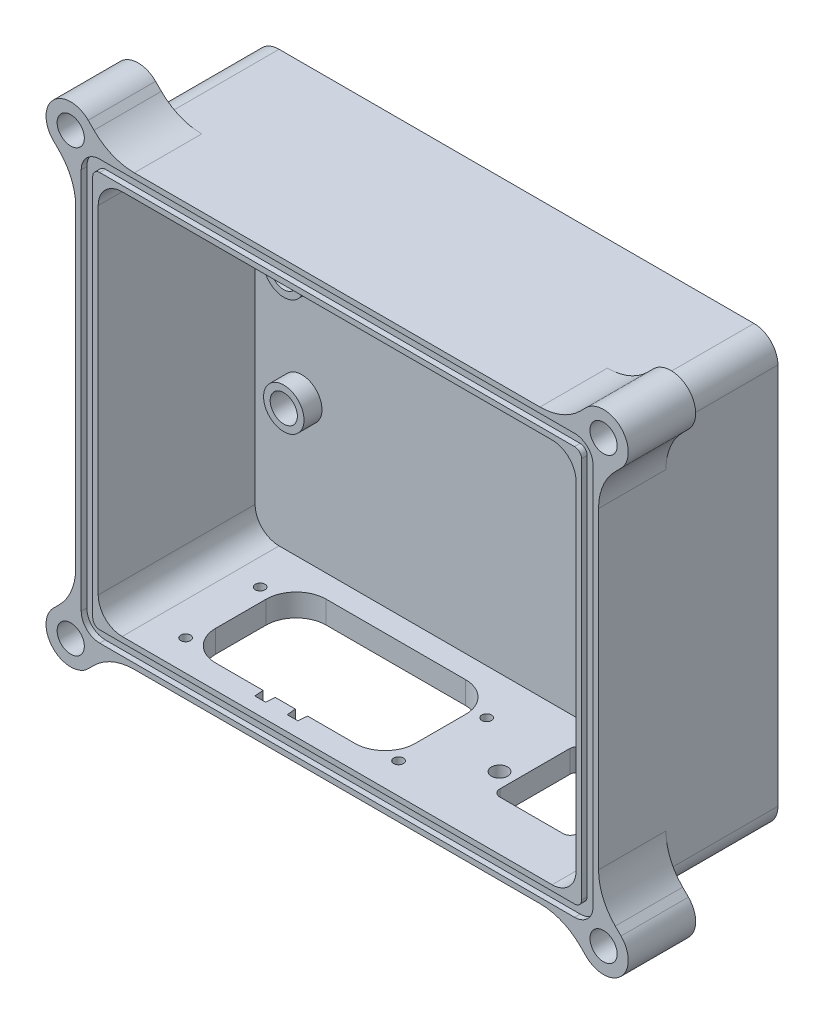
SolidWorks part; units mm, degrees
material "ABS"
ref_plane "X-Y Datum" through (0, 0, 0) normal (0, 0, 1) x (1, 0, 0)
ref_plane "X-Z Datum" through (0, 0, 0) normal (0, 1, 0) x (1, 0, 0)
ref_plane "Y-Z Datum" through (0, 0, 0) normal (1, 0, 0) x (0, 0, -1)
sketch "Sketch1" plane through (0, 0, 0) normal (0, 0, 1) x (1, 0, 0)
  line L1 (-53.1813, 42.8625) -> (53.1812, 42.8625)
  line L2 (-53.1813, 42.8625) -> (-53.1812, -42.8625)
  line L3 (-53.1812, -42.8625) -> (53.1813, -42.8625)
  line L4 (53.1812, 42.8625) -> (53.1813, -42.8625)
  line L5 (-53.1813, 42.8625) -> (53.1813, -42.8625) construction
  line L6 (-53.1812, -42.8625) -> (53.1812, 42.8625) construction
  point P0 (0, 0)
  dimension "D1" = 106.3625
  dimension "D2" = 85.725
extrude "Boss-Extrude1" add sketch "Sketch1" along normal blind 34.925
shell "Shell1" thickness 5 removed face at (0, 0, 34.925) outward yes
fillet "Fillet1" radius 5.334 8 edges at (-58.1812, -47.8625, 14.9625) (58.1813, -47.8625, 14.9625) (53.1812, 42.8625, 17.4625) (58.1812, 47.8625, 14.9625) (-58.1813, 47.8625, 14.9625) (-53.1813, 42.8625, 17.4625) (53.1813, -42.8625, 17.4625) (-53.1812, -42.8625, 17.4625)
sketch "Sketch2" plane through (0, 0, 34.925) normal (0, 0, 1) x (1, 0, 0)
  line L20 (-52.8472, -46.6452) -> (52.8472, -46.6452)
  line L21 (56.9639, -42.5285) -> (56.9639, 42.5285)
  line L22 (52.8472, 46.6452) -> (-52.8473, 46.6452)
  line L23 (-56.9639, 42.5285) -> (-56.9639, -42.5285)
  line L24 (-52.8472, -45.3625) -> (52.8473, -45.3625)
  line L25 (55.6812, -42.5285) -> (55.6812, 42.5285)
  line L26 (52.8472, 45.3625) -> (-52.8473, 45.3625)
  line L27 (-55.6812, 42.5285) -> (-55.6812, -42.5285)
  line L28 (-52.8472, -45.3625) -> (52.8473, -45.3625) construction
  line L29 (55.6812, -42.5285) -> (55.6812, 42.5285) construction
  line L30 (52.8472, 45.3625) -> (-52.8473, 45.3625) construction
  line L31 (-55.6812, 42.5285) -> (-55.6812, -42.5285) construction
  line L32 (-54.3986, 42.5285) -> (-54.3986, -42.5285)
  line L33 (-52.8472, -44.0798) -> (52.8472, -44.0798)
  line L34 (54.3986, -42.5285) -> (54.3986, 42.5285)
  line L35 (52.8472, 44.0798) -> (-52.8473, 44.0798)
  arc A16 (52.8472, -46.6452) -> (56.9639, -42.5285) centre (52.8473, -42.5285) ccw
  arc A17 (56.9639, 42.5285) -> (52.8472, 46.6452) centre (52.8472, 42.5285) ccw
  arc A18 (-52.8473, 46.6452) -> (-56.9639, 42.5285) centre (-52.8473, 42.5285) ccw
  arc A19 (-56.9639, -42.5285) -> (-52.8472, -46.6452) centre (-52.8472, -42.5285) ccw
  arc A20 (-55.6812, -42.5285) -> (-52.8472, -45.3625) centre (-52.8472, -42.5285) ccw
  arc A21 (52.8473, -45.3625) -> (55.6812, -42.5285) centre (52.8473, -42.5285) ccw
  arc A22 (55.6812, 42.5285) -> (52.8472, 45.3625) centre (52.8472, 42.5285) ccw
  arc A23 (-52.8473, 45.3625) -> (-55.6812, 42.5285) centre (-52.8473, 42.5285) ccw
  arc A24 (-55.6812, -42.5285) -> (-52.8472, -45.3625) centre (-52.8472, -42.5285) ccw construction
  arc A25 (52.8473, -45.3625) -> (55.6812, -42.5285) centre (52.8473, -42.5285) ccw construction
  arc A26 (55.6812, 42.5285) -> (52.8472, 45.3625) centre (52.8472, 42.5285) ccw construction
  arc A27 (-52.8473, 45.3625) -> (-55.6812, 42.5285) centre (-52.8473, 42.5285) ccw construction
  arc A28 (-52.8473, 44.0798) -> (-54.3986, 42.5285) centre (-52.8473, 42.5285) ccw
  arc A29 (-54.3986, -42.5285) -> (-52.8472, -44.0798) centre (-52.8472, -42.5285) ccw
  arc A30 (52.8472, -44.0798) -> (54.3986, -42.5285) centre (52.8473, -42.5285) ccw
  arc A31 (54.3986, 42.5285) -> (52.8472, 44.0798) centre (52.8472, 42.5285) ccw
  dimension "D4" = 2.5654
  dimension "D1" = 2.5
  dimension "D2" = 1.2827
  dimension "D3" = 1.2827
extrude "Cut-Extrude1" cut sketch "Sketch2" against normal blind 1.2446
sketch "Sketch4" plane through (0, 0, 34.925) normal (0, 0, 1) x (1, 0, 0)
  line L4 (58.1813, -42.5285) -> (58.1812, 42.5285) construction
  line L6 (47.8473, -37.5285) -> (59.2937, -48.975)
  line L7 (55.4046, -52.8641) -> (50.4031, -47.8625)
  line L8 (-52.8472, -47.8625) -> (52.8473, -47.8625) construction
  line L9 (63.1828, -45.0859) -> (58.1813, -40.0843)
  line L10 (-52.8472, -47.8625) -> (52.8473, -47.8625)
  line L11 (58.1813, -42.5285) -> (58.1812, 42.5285)
  arc A2 (47.8473, -42.8625) -> (53.1813, -37.5285) centre (47.8473, -37.5285) ccw construction
  circle A3 centre (59.2937, -48.975) radius 3.025
  circle A4 centre (59.2937, -48.975) radius 5.5
  arc A5 (52.8472, -46.6452) -> (56.9639, -42.5285) centre (52.8473, -42.5285) ccw construction
  arc A6 (52.8473, -47.8625) -> (58.1813, -42.5285) centre (52.8473, -42.5285) ccw construction
  arc A7 (58.1812, 42.5285) -> (52.8472, 47.8625) centre (52.8472, 42.5285) ccw construction
  arc A8 (52.8473, -47.8625) -> (58.1813, -42.5285) centre (52.8473, -42.5285) ccw
  arc A9 (58.1812, 42.5285) -> (52.8472, 47.8625) centre (52.8472, 42.5285) ccw
  point P14 (51.619, -41.3002)
  point P23 (55.7582, -45.4394)
  dimension "D1" = 11
  dimension "D2" = 6.05
  dimension "D4" = 5
extrude "Boss-Extrude2" add sketch "Sketch4" against normal blind 15 separate body contours A9 L11 | A9 | A8 A4 L9 L11 | A8 L10 L7 A4 | A8 A4 A3 | A3 | L11 region at (60.4186, -46.2593, 34.925) region at (57.6777, -45.1365, 34.925) region at (59.5123, -42.505, 34.925) region at (52.8237, -49.1935, 34.925)
sketch "Sketch5" plane through (0, 0, 34.925) normal (0, 0, 1) x (1, 0, 0)
  line L3 (-52.8472, -47.8625) -> (52.8473, -47.8625) construction
  line L4 (63.1828, -45.0859) -> (58.1813, -40.0843) construction
  line L5 (55.4046, -52.8641) -> (50.4031, -47.8625) construction
  line L6 (47.8473, -37.5285) -> (59.2937, -48.975) construction
  line L10 (-52.8472, -47.8625) -> (52.8473, -47.8625)
  line L11 (63.1828, -45.0859) -> (58.1813, -40.0843)
  line L12 (55.4046, -52.8641) -> (50.4031, -47.8625)
  line L13 (47.8473, -37.5285) -> (59.2937, -48.975)
  circle A1 centre (59.2937, -48.975) radius 3.025
  circle A2 centre (59.2937, -48.975) radius 3.025
  circle A7 centre (59.2937, -48.975) radius 5.5
  circle A8 centre (59.2937, -48.975) radius 5.5
  arc A9 (52.8473, -47.8625) -> (58.1813, -42.5285) centre (52.8473, -42.5285) ccw construction
  arc A11 (52.8473, -47.8625) -> (58.1813, -42.5285) centre (52.8473, -42.5285) ccw
  dimension "D1" = 0
  dimension "D4" = 0
extrude "Cut-Extrude4" cut sketch "Sketch5" against normal blind 8 contours A2 region at (60.4186, -46.2593, 34.925)
mirror "Mirror3" about plane through (0, 0, 0) normal (1, 0, 0) of bodies 107 106
mirror "Mirror7" about plane through (0, 0, 0) normal (0, 1, 0) of bodies 107 109
combine bodies "Combine3" operation type add bodies to combine 102 107 109 121 122
fillet "Fillet2" radius 12.7 8 edges at (-50.4031, -47.8625, 27.425) (-58.1813, -40.0843, 27.425) (50.4031, -47.8625, 27.425) (58.1813, -40.0843, 27.425) (-58.1813, 40.0843, 27.425) (-50.4031, 47.8625, 27.425) (50.4031, 47.8625, 27.425) (58.1813, 40.0843, 27.425)
sketch "Sketch13" plane through (0, -47.8625, 0) normal (0, -1, 0) x (1, 0, 0)
  line L0 (-12.3227, 29.1278) -> (-12.4976, 31.1278) construction
  line L1 (-12.4976, 31.1278) -> (-13.9477, 31.1278) construction
  line L2 (-13.9477, 31.1278) -> (-14.1227, 29.1278) construction
  line L3 (-19.6976, 31.1278) -> (-21.1477, 31.1278) construction
  line L4 (-21.1477, 31.1278) -> (-21.3227, 29.1278) construction
  line L5 (-19.5227, 29.1278) -> (-19.6976, 31.1278) construction
  line L6 (-21.3227, 29.1278) -> (-32.3227, 29.1278) construction
  line L7 (-38.5227, 22.9278) -> (-38.5227, 11.7278) construction
  line L8 (-32.3227, 5.5278) -> (-1.3227, 5.5278) construction
  line L9 (4.8773, 11.7278) -> (4.8773, 22.9278) construction
  line L10 (-1.3227, 29.1278) -> (-12.3227, 29.1278) construction
  line L11 (-14.1227, 29.1278) -> (-19.5227, 29.1278) construction
  line L52 (-12.3227, 29.1278) -> (-12.4976, 31.1278) construction
  line L53 (-12.4976, 31.1278) -> (-13.9477, 31.1278) construction
  line L54 (-13.9477, 31.1278) -> (-14.1227, 29.1278) construction
  line L55 (-19.6976, 31.1278) -> (-21.1477, 31.1278) construction
  line L67 (24.0563, 22.2478) -> (24.0563, 6.6978) construction
  line L80 (-21.1477, 31.1278) -> (-21.3227, 29.1278) construction
  line L81 (-19.5227, 29.1278) -> (-19.6976, 31.1278) construction
  line L82 (-21.3227, 29.1278) -> (-32.3227, 29.1278) construction
  line L83 (-38.5227, 22.9278) -> (-38.5227, 11.7278) construction
  line L84 (-32.3227, 5.5278) -> (-1.3227, 5.5278) construction
  line L85 (4.8773, 11.7278) -> (4.8773, 22.9278) construction
  line L86 (-1.3227, 29.1278) -> (-12.3227, 29.1278) construction
  line L87 (-14.1227, 29.1278) -> (-19.5227, 29.1278) construction
  line L88 (-11.8645, 29.6278) -> (-12.0395, 31.6278)
  line L89 (-12.0395, 31.6278) -> (-14.4059, 31.6278)
  line L90 (-14.4059, 31.6278) -> (-14.5808, 29.6278)
  line L91 (-14.5808, 29.6278) -> (-19.0645, 29.6278)
  line L92 (-19.0645, 29.6278) -> (-19.2395, 31.6278)
  line L93 (-19.2395, 31.6278) -> (-21.6059, 31.6278)
  line L94 (-21.6059, 31.6278) -> (-21.7808, 29.6278)
  line L95 (-21.7808, 29.6278) -> (-32.3227, 29.6278)
  line L96 (-39.0227, 22.9278) -> (-39.0227, 11.7278)
  line L97 (-32.3227, 5.0278) -> (-1.3227, 5.0278)
  line L98 (5.3773, 11.7278) -> (5.3773, 22.9278)
  line L99 (-1.3227, 29.6278) -> (-11.8645, 29.6278)
  line L100 (25.1563, 5.5978) -> (39.2063, 5.5978) construction
  line L101 (40.3063, 6.6978) -> (40.3063, 22.2478) construction
  line L102 (39.2063, 23.3478) -> (25.1563, 23.3478) construction
  line L103 (24.0563, 22.2478) -> (24.0563, 6.6978) construction
  line L104 (25.1563, 5.5978) -> (39.2063, 5.5978) construction
  line L105 (40.3063, 6.6978) -> (40.3063, 22.2478) construction
  line L106 (39.2063, 23.3478) -> (25.1563, 23.3478) construction
  line L107 (23.5563, 22.2478) -> (23.5563, 6.6978)
  line L124 (25.1563, 5.0978) -> (39.2063, 5.0978)
  line L125 (40.8063, 6.6978) -> (40.8063, 22.2478)
  line L126 (39.2063, 23.8478) -> (25.1563, 23.8478)
  arc A0 (24.0563, 6.6978) -> (25.1563, 5.5978) centre (25.1563, 6.6978) ccw construction
  arc A1 (39.2063, 5.5978) -> (40.3063, 6.6978) centre (39.2063, 6.6978) ccw construction
  arc A2 (40.3063, 22.2478) -> (39.2063, 23.3478) centre (39.2063, 22.2478) ccw construction
  arc A3 (25.1563, 23.3478) -> (24.0563, 22.2478) centre (25.1563, 22.2478) ccw construction
  arc A12 (24.0563, 6.6978) -> (25.1563, 5.5978) centre (25.1563, 6.6978) ccw construction
  arc A13 (39.2063, 5.5978) -> (40.3063, 6.6978) centre (39.2063, 6.6978) ccw construction
  arc A14 (40.3063, 22.2478) -> (39.2063, 23.3478) centre (39.2063, 22.2478) ccw construction
  arc A15 (25.1563, 23.3478) -> (24.0563, 22.2478) centre (25.1563, 22.2478) ccw construction
  arc A24 (23.5563, 6.6978) -> (25.1563, 5.0978) centre (25.1563, 6.6978) ccw
  arc A25 (39.2063, 5.0978) -> (40.8063, 6.6978) centre (39.2063, 6.6978) ccw
  arc A26 (40.8063, 22.2478) -> (39.2063, 23.8478) centre (39.2063, 22.2478) ccw
  arc A27 (25.1563, 23.8478) -> (23.5563, 22.2478) centre (25.1563, 22.2478) ccw
  spline S0 degree 3 poles (-32.3227, 29.1278) (-35.9545, 29.1278) (-38.5227, 26.5597) (-38.5227, 22.9278) knots 0 0 0 0 1 1 1 1 weights 1 0.804738 0.804738 1 construction
  spline S1 degree 3 poles (-38.5227, 11.7278) (-38.5227, 8.0959) (-35.9545, 5.5278) (-32.3227, 5.5278) knots 0 0 0 0 1 1 1 1 weights 1 0.804738 0.804738 1 construction
  spline S2 degree 3 poles (-1.3227, 5.5278) (2.3092, 5.5278) (4.8773, 8.0959) (4.8773, 11.7278) knots 0 0 0 0 1 1 1 1 weights 1 0.804738 0.804738 1 construction
  spline S3 degree 3 poles (4.8773, 22.9278) (4.8773, 26.5597) (2.3092, 29.1278) (-1.3227, 29.1278) knots 0 0 0 0 1 1 1 1 weights 1 0.804738 0.804738 1 construction
  spline S4 degree 3 poles (-32.3227, 29.1278) (-35.9545, 29.1278) (-38.5227, 26.5597) (-38.5227, 22.9278) knots 0 0 0 0 1 1 1 1 weights 1 0.804738 0.804738 1 construction
  spline S5 degree 3 poles (-38.5227, 11.7278) (-38.5227, 8.0959) (-35.9545, 5.5278) (-32.3227, 5.5278) knots 0 0 0 0 1 1 1 1 weights 1 0.804738 0.804738 1 construction
  spline S6 degree 3 poles (-1.3227, 5.5278) (2.3092, 5.5278) (4.8773, 8.0959) (4.8773, 11.7278) knots 0 0 0 0 1 1 1 1 weights 1 0.804738 0.804738 1 construction
  spline S7 degree 3 poles (4.8773, 22.9278) (4.8773, 26.5597) (2.3092, 29.1278) (-1.3227, 29.1278) knots 0 0 0 0 1 1 1 1 weights 1 0.804738 0.804738 1 construction
  spline S8 degree 1 poles (-32.3227, 29.6278) (-39.0227, 22.9278) knots 0 0 1 1 construction
  spline S9 degree 1 poles (-39.0227, 11.7278) (-32.3227, 5.0278) knots 0 0 1 1 construction
  spline S10 degree 1 poles (-1.3227, 5.0278) (5.3773, 11.7278) knots 0 0 1 1 construction
  spline S11 degree 1 poles (5.3773, 22.9278) (-1.3227, 29.6278) knots 0 0 1 1 construction
  spline S12 degree 3 poles (-32.3227, 29.6278) (-32.7308, 29.6278) (-33.5306, 29.5573) (-35.22, 29.0854) (-37.2004, 27.8055) (-38.4803, 25.8252) (-38.9522, 24.1358) (-39.0227, 23.3359) (-39.0227, 22.9278) knots 0 0 0 0 0.125 0.25 0.5 0.75 0.875 1 1 1 1
  spline S13 degree 3 poles (-39.0227, 11.7278) (-39.0227, 11.3197) (-38.9522, 10.5199) (-38.4803, 8.8305) (-37.2004, 6.8501) (-35.22, 5.5702) (-33.5306, 5.0983) (-32.7308, 5.0278) (-32.3227, 5.0278) knots 0 0 0 0 0.125 0.25 0.5 0.75 0.875 1 1 1 1
  spline S14 degree 3 poles (-1.3227, 5.0278) (-0.9146, 5.0278) (-0.1147, 5.0983) (1.5747, 5.5702) (3.555, 6.8501) (4.8349, 8.8305) (5.3068, 10.5199) (5.3773, 11.3197) (5.3773, 11.7278) knots 0 0 0 0 0.125 0.25 0.5 0.75 0.875 1 1 1 1
  spline S15 degree 3 poles (5.3773, 22.9278) (5.3773, 23.3359) (5.3068, 24.1358) (4.8349, 25.8252) (3.555, 27.8055) (1.5747, 29.0854) (-0.1147, 29.5573) (-0.9146, 29.6278) (-1.3227, 29.6278) knots 0 0 0 0 0.125 0.25 0.5 0.75 0.875 1 1 1 1
  spline S16 degree 3 poles (-43.1077, 10.0278) (-43.1077, 12.1978) (-40.9377, 12.1978) (-40.9377, 10.0278) knots 0 0 0 0 1 1 1 1 weights 1 0.333333 0.333333 1 construction
  spline S17 degree 3 poles (-40.9377, 10.0278) (-40.9377, 7.8578) (-43.1077, 7.8578) (-43.1077, 10.0278) knots 0 0 0 0 1 1 1 1 weights 1 0.333333 0.333333 1 construction
  spline S18 degree 3 poles (-41.6077, 28.1278) (-41.6077, 30.2978) (-39.4377, 30.2978) (-39.4377, 28.1278) knots 0 0 0 0 1 1 1 1 weights 1 0.333333 0.333333 1 construction
  spline S19 degree 3 poles (-39.4377, 28.1278) (-39.4377, 25.9578) (-41.6077, 25.9578) (-41.6077, 28.1278) knots 0 0 0 0 1 1 1 1 weights 1 0.333333 0.333333 1 construction
  spline S20 degree 3 poles (-43.1077, 10.0278) (-43.1077, 12.1978) (-40.9377, 12.1978) (-40.9377, 10.0278) knots 0 0 0 0 1 1 1 1 weights 1 0.333333 0.333333 1
  spline S21 degree 3 poles (-40.9377, 10.0278) (-40.9377, 7.8578) (-43.1077, 7.8578) (-43.1077, 10.0278) knots 0 0 0 0 1 1 1 1 weights 1 0.333333 0.333333 1
  spline S22 degree 3 poles (-41.6077, 28.1278) (-41.6077, 30.2978) (-39.4377, 30.2978) (-39.4377, 28.1278) knots 0 0 0 0 1 1 1 1 weights 1 0.333333 0.333333 1
  spline S23 degree 3 poles (-39.4377, 28.1278) (-39.4377, 25.9578) (-41.6077, 25.9578) (-41.6077, 28.1278) knots 0 0 0 0 1 1 1 1 weights 1 0.333333 0.333333 1
  spline S24 degree 3 poles (7.9623, 28.1278) (7.9623, 25.9578) (5.7923, 25.9578) (5.7923, 28.1278) knots 0 0 0 0 1 1 1 1 weights 1 0.333333 0.333333 1 construction
  spline S25 degree 3 poles (5.7923, 28.1278) (5.7923, 30.2978) (7.9623, 30.2978) (7.9623, 28.1278) knots 0 0 0 0 1 1 1 1 weights 1 0.333333 0.333333 1 construction
  spline S26 degree 3 poles (7.9623, 28.1278) (7.9623, 25.9578) (5.7923, 25.9578) (5.7923, 28.1278) knots 0 0 0 0 1 1 1 1 weights 1 0.333333 0.333333 1
  spline S27 degree 3 poles (5.7923, 28.1278) (5.7923, 30.2978) (7.9623, 30.2978) (7.9623, 28.1278) knots 0 0 0 0 1 1 1 1 weights 1 0.333333 0.333333 1
  spline S28 degree 3 poles (9.4623, 10.0278) (9.4623, 7.8578) (7.2923, 7.8578) (7.2923, 10.0278) knots 0 0 0 0 1 1 1 1 weights 1 0.333333 0.333333 1 construction
  spline S29 degree 3 poles (7.2923, 10.0278) (7.2923, 12.1978) (9.4623, 12.1978) (9.4623, 10.0278) knots 0 0 0 0 1 1 1 1 weights 1 0.333333 0.333333 1 construction
  spline S30 degree 3 poles (7.2923, 10.0278) (7.2923, 12.1978) (9.4623, 12.1978) (9.4623, 10.0278) knots 0 0 0 0 1 1 1 1 weights 1 0.333333 0.333333 1
  spline S31 degree 3 poles (9.4623, 10.0278) (9.4623, 7.8578) (7.2923, 7.8578) (7.2923, 10.0278) knots 0 0 0 0 1 1 1 1 weights 1 0.333333 0.333333 1
  point P47 (20.1813, 18.9728)
  point P48 (44.1813, 9.9728)
  dimension "D1" = 0.5
  dimension "D2" = 0.5
extrude "Cut-Extrude6" cut sketch "Sketch13" against normal blind 5 contours L126 A27 L107 A24 L124 A25 L125 A26 | L98 S15 L99 L88 L89 L90 L91 L92 L93 L94 L95 S12 L96 S13 L97 S14 | S27 S26 | S31 S30 | S23 S22 | S21 S20 region at (-16.8227, -47.8625, 17.4547) region at (32.1813, -47.8625, 14.4728) region at (-42.0227, -47.8625, 10.0278) region at (-40.5227, -47.8625, 28.1278) region at (6.8773, -47.8625, 28.1278) region at (8.3773, -47.8625, 10.0278)
hole_wizard "M3 Clearance Hole1" positions "Sketch17" profile "Sketch15" hole size "M3" standard "ANSI Metric"
sketch "Sketch17" plane through (0, -47.8625, 0) normal (0, -1, 0) x (-1, 0, 0)
  point P10 (-20.1813, -18.9728)
  point P13 (-44.1813, -9.9728)
sketch "Sketch15" plane through (20.1813, -47.8625, 18.9728) normal (1, 0, 0) x (0, 0, -1)
  line L0 (0, 0) -> (0, 6.0815)
  line L1 (0, 6.0815) -> (1.8, 5)
  line L2 (1.8, 5) -> (1.8, 0)
  line L5 (1.8, 0) -> (0, 0)
  line L10 (0, 6.0815) -> (-1.8, 5) construction
  line L11 (0, -6.35) -> (0, 107.95) construction
  dimension "Hole Dia." = 3.6
  dimension "Hole Depth" = 5
  dimension "Drill Angle" = 118
sketch "Sketch18" plane through (0, 0, 0) normal (0, 0, 1) x (1, 0, 0)
  circle A0 centre (-42.8028, 14.0785) radius 3.025
  circle A1 centre (-42.8028, -11.8295) radius 3.025
  circle A2 centre (28.9332, -12.9535) radius 3.025
  circle A3 centre (28.9332, 14.9865) radius 3.025
  circle A4 centre (-42.8028, 14.0785) radius 4.5
  circle A5 centre (-42.8028, -11.8295) radius 4.5
  circle A6 centre (28.9332, 14.9865) radius 4.5
  circle A7 centre (28.9332, -12.9535) radius 4.5
  point P0 (-42.8028, 14.0785)
  point P1 (-42.8028, -11.8295)
  point P3 (28.9332, -12.9535)
  point P5 (28.9332, 14.9865)
  dimension "D1" = 6.05
  dimension "D2" = 9
extrude "Boss-Extrude3" add sketch "Sketch18" along normal blind 4
sketch "Sketch19" plane through (0, 0, 0) normal (0, 0, 1) x (1, 0, 0)
  circle A0 centre (28.9332, 14.9865) radius 3.025 construction
  circle A1 centre (28.9332, -12.9535) radius 3.025 construction
  circle A2 centre (-42.8028, -11.8295) radius 3.025 construction
  circle A3 centre (-42.8028, 14.0785) radius 3.025 construction
  circle A4 centre (28.9332, 14.9865) radius 3.025
  circle A5 centre (28.9332, -12.9535) radius 3.025
  circle A6 centre (-42.8028, -11.8295) radius 3.025
  circle A7 centre (-42.8028, 14.0785) radius 3.025
extrude "Cut-Extrude7" cut sketch "Sketch19" against normal blind 1.5
